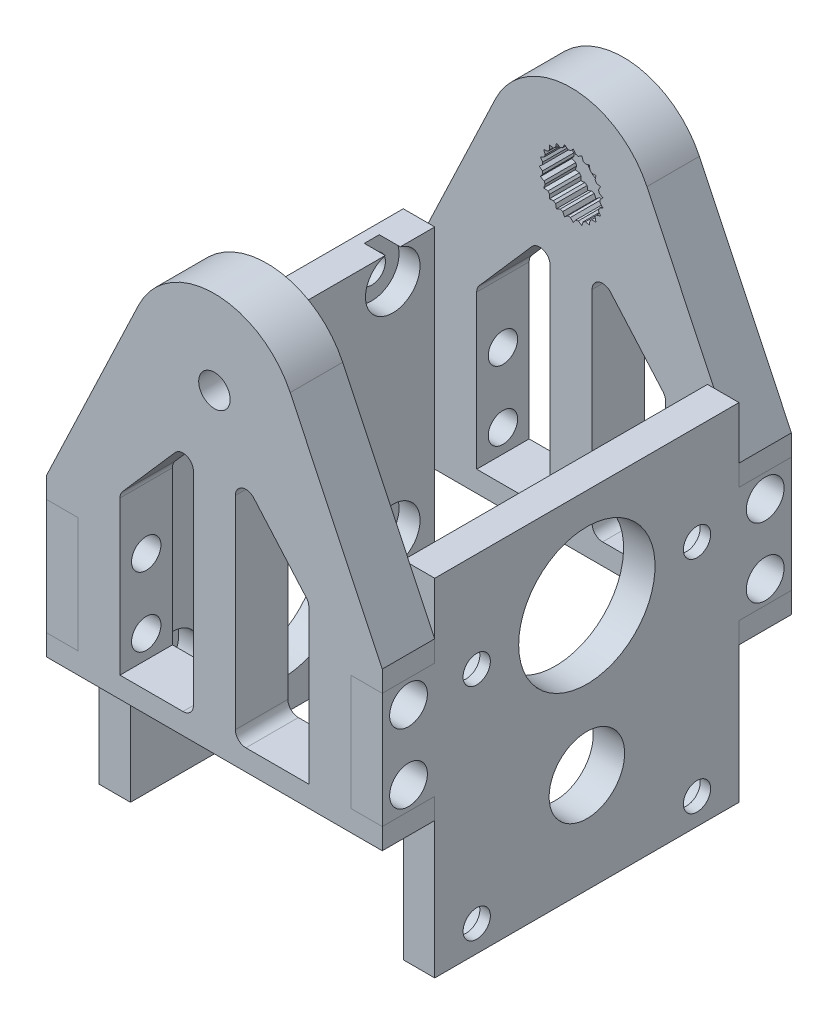
SolidWorks part; units mm, degrees
ref_plane "正面" through (0, 0, 0) normal (0, 0, 1) x (1, 0, 0)
ref_plane "平面" through (0, 0, 0) normal (0, 1, 0) x (1, 0, 0)
ref_plane "右側面" through (0, 0, 0) normal (1, 0, 0) x (0, 0, -1)
sketch "ｽｹｯﾁ1" plane through (0, 0, 0) normal (0, 0, 1) x (1, 0, 0)
  line L0 (-16, -15) -> (-16, -30)
  line L1 (-16, -30) -> (16, -30)
  line L2 (16, -30) -> (16, -15)
  line L3 (16, -15) -> (7.2234, 3.4383)
  line L4 (-7.2234, 3.4383) -> (-16, -15)
  line L5 (0, 0) -> (0, -30) construction
  line L6 (-16, -15) -> (16, -15) construction
  circle A0 centre (0, 0) radius 2.75
  arc A1 (7.2234, 3.4383) -> (-7.2234, 3.4383) centre (0, 0) ccw
  dimension "D1" = 5.5
  dimension "D6" = 8
  dimension "D2" = 16
  dimension "D3" = 16
  dimension "D4" = 15
  dimension "D5" = 15
extrude "ﾎﾞｽ - 押し出し1" add sketch "ｽｹｯﾁ1" along normal blind 3
sketch "ｽｹｯﾁ19" plane through (0, 0, 3) normal (0, 0, 1) x (1, 0, 0)
  line L0 (0, 0) -> (0, 2.75) construction
  line L1 (0, 0) -> (0.3745, 2.7244) construction
  line L2 (0, 0) -> (0.7419, 2.648) construction
  line L3 (0, 0) -> (1.0956, 2.5223) construction
  line L4 (0, 0) -> (1.4289, 2.3497) construction
  line L5 (0, 0) -> (1.7355, 2.1332) construction
  line L6 (0, 0) -> (2.0098, 1.877) construction
  line L7 (0, 0) -> (2.2467, 1.5859) construction
  line L8 (0, 0) -> (2.4417, 1.2652) construction
  line L9 (0, 0) -> (2.5912, 0.9209) construction
  line L10 (0, 0) -> (2.6925, 0.5595) construction
  line L11 (0, 0) -> (2.7436, 0.1877) construction
  line L12 (0, 0) -> (2.7436, -0.1877) construction
  line L13 (0, 0) -> (2.6925, -0.5595) construction
  line L14 (0, 0) -> (2.5912, -0.9209) construction
  line L15 (0, 0) -> (2.4417, -1.2652) construction
  line L16 (0, 0) -> (2.2467, -1.5859) construction
  line L17 (0, 0) -> (2.0098, -1.877) construction
  line L18 (0, 0) -> (1.7355, -2.1332) construction
  line L19 (0, 0) -> (1.4289, -2.3497) construction
  line L20 (0, 0) -> (1.0956, -2.5223) construction
  line L21 (0, 0) -> (0.7419, -2.648) construction
  line L22 (0, 0) -> (0.3745, -2.7244) construction
  line L23 (0, 0) -> (0, -2.75) construction
  line L24 (0, 0) -> (-0.3745, -2.7244) construction
  line L25 (0, 0) -> (-0.7419, -2.648) construction
  line L26 (0, 0) -> (-1.0956, -2.5223) construction
  line L27 (0, 0) -> (-1.4289, -2.3497) construction
  line L28 (0, 0) -> (-1.7355, -2.1332) construction
  line L29 (0, 0) -> (-2.0098, -1.877) construction
  line L30 (0, 0) -> (-2.2467, -1.5859) construction
  line L31 (0, 0) -> (-2.4417, -1.2652) construction
  line L32 (0, 0) -> (-2.5912, -0.9209) construction
  line L33 (0, 0) -> (-2.6925, -0.5595) construction
  line L34 (0, 0) -> (-2.7436, -0.1877) construction
  line L35 (0, 0) -> (-2.7436, 0.1877) construction
  line L36 (0, 0) -> (-2.6925, 0.5595) construction
  line L37 (0, 0) -> (-2.5912, 0.9209) construction
  line L38 (0, 0) -> (-2.4417, 1.2652) construction
  line L39 (0, 0) -> (-2.2467, 1.5859) construction
  line L40 (0, 0) -> (-2.0098, 1.877) construction
  line L41 (0, 0) -> (-1.7355, 2.1332) construction
  line L42 (0, 0) -> (-1.4289, 2.3497) construction
  line L43 (0, 0) -> (-1.0956, 2.5223) construction
  line L44 (0, 0) -> (-0.7419, 2.648) construction
  line L45 (0, 0) -> (-0.3745, 2.7244) construction
  line L46 (0, 0) -> (0.2081, 3.0429) construction
  line L47 (0.2081, 3.0429) -> (-0.0626, 2.7493)
  line L48 (0.2081, 3.0429) -> (0.4364, 2.7152)
  line L49 (-0.0626, 2.7493) -> (0, 0) construction
  line L50 (0, 0) -> (0.4364, 2.7152) construction
  line L51 (1.0214, 2.8739) -> (0.6815, 2.6642)
  line L52 (1.0214, 2.8739) -> (1.1527, 2.4967)
  line L53 (1.7589, 2.4918) -> (1.375, 2.3816)
  line L54 (1.7589, 2.4918) -> (1.7836, 2.0931)
  line L55 (2.3659, 1.9248) -> (1.9666, 1.9223)
  line L56 (2.3659, 1.9248) -> (2.2822, 1.5343)
  line L57 (2.7975, 1.2151) -> (2.4123, 1.3204)
  line L58 (2.7975, 1.2151) -> (2.6115, 0.8617)
  line L59 (3.0216, 0.4153) -> (2.679, 0.6206)
  line L60 (3.0216, 0.4153) -> (2.7472, 0.1252)
  line L61 (3.0216, -0.4153) -> (2.7472, -0.1252)
  line L62 (3.0216, -0.4153) -> (2.679, -0.6206)
  line L63 (2.7975, -1.2151) -> (2.6115, -0.8617)
  line L64 (2.7975, -1.2151) -> (2.4123, -1.3204)
  line L65 (2.3659, -1.9248) -> (2.2822, -1.5343)
  line L66 (2.3659, -1.9248) -> (1.9666, -1.9223)
  line L67 (1.7589, -2.4918) -> (1.7836, -2.0931)
  line L68 (1.7589, -2.4918) -> (1.375, -2.3816)
  line L69 (1.0214, -2.8739) -> (1.1527, -2.4967)
  line L70 (1.0214, -2.8739) -> (0.6815, -2.6642)
  line L71 (0.2081, -3.0429) -> (0.4364, -2.7152)
  line L72 (0.2081, -3.0429) -> (-0.0626, -2.7493)
  line L73 (-0.6205, -2.9862) -> (-0.3123, -2.7322)
  line L74 (-0.6205, -2.9862) -> (-0.802, -2.6304)
  line L75 (-1.4032, -2.708) -> (-1.0379, -2.5466)
  line L76 (-1.4032, -2.708) -> (-1.482, -2.3165)
  line L77 (-2.0818, -2.229) -> (-1.6865, -2.1722)
  line L78 (-2.0818, -2.229) -> (-2.052, -1.8308)
  line L79 (-2.606, -1.5847) -> (-2.21, -1.6366)
  line L80 (-2.606, -1.5847) -> (-2.4699, -1.2093)
  line L81 (-2.9369, -0.8229) -> (-2.5696, -0.9797)
  line L82 (-2.9369, -0.8229) -> (-2.7045, -0.4981)
  line L83 (-3.05, 0) -> (-2.7386, -0.2501)
  line L84 (-3.05, 0) -> (-2.7386, 0.2501)
  line L85 (-2.9369, 0.8229) -> (-2.7045, 0.4981)
  line L86 (-2.9369, 0.8229) -> (-2.5696, 0.9797)
  line L87 (-2.606, 1.5847) -> (-2.4699, 1.2093)
  line L88 (-2.606, 1.5847) -> (-2.21, 1.6366)
  line L89 (-2.0818, 2.229) -> (-2.052, 1.8308)
  line L90 (-2.0818, 2.229) -> (-1.6865, 2.1722)
  line L91 (-1.4032, 2.708) -> (-1.482, 2.3165)
  line L92 (-1.4032, 2.708) -> (-1.0379, 2.5466)
  line L93 (-0.6205, 2.9862) -> (-0.802, 2.6304)
  line L94 (-0.6205, 2.9862) -> (-0.3123, 2.7322)
  circle A0 centre (0, 0) radius 2.75 construction
  arc A1 (0, 2.75) -> (0.3745, 2.7244) centre (0, 0) cw construction
  circle A2 centre (0, 0) radius 3.05 construction
  arc A3 (-0.0626, 2.7493) -> (0.4364, 2.7152) centre (0, 0) cw
  arc A4 (0.6815, 2.6642) -> (1.1527, 2.4967) centre (0, 0) cw
  arc A5 (1.375, 2.3816) -> (1.7836, 2.0931) centre (0, 0) cw
  arc A6 (1.9666, 1.9223) -> (2.2822, 1.5343) centre (0, 0) cw
  arc A7 (2.4123, 1.3204) -> (2.6115, 0.8617) centre (0, 0) cw
  arc A8 (2.679, 0.6206) -> (2.7472, 0.1252) centre (0, 0) cw
  arc A9 (2.7472, -0.1252) -> (2.679, -0.6206) centre (0, 0) cw
  arc A10 (2.6115, -0.8617) -> (2.4123, -1.3204) centre (0, 0) cw
  arc A11 (2.2822, -1.5343) -> (1.9666, -1.9223) centre (0, 0) cw
  arc A12 (1.7836, -2.0931) -> (1.375, -2.3816) centre (0, 0) cw
  arc A13 (1.1527, -2.4967) -> (0.6815, -2.6642) centre (0, 0) cw
  arc A14 (0.4364, -2.7152) -> (-0.0626, -2.7493) centre (0, 0) cw
  arc A15 (-0.3123, -2.7322) -> (-0.802, -2.6304) centre (0, 0) cw
  arc A16 (-1.0379, -2.5466) -> (-1.482, -2.3165) centre (0, 0) cw
  arc A17 (-1.6865, -2.1722) -> (-2.052, -1.8308) centre (0, 0) cw
  arc A18 (-2.21, -1.6366) -> (-2.4699, -1.2093) centre (0, 0) cw
  arc A19 (-2.5696, -0.9797) -> (-2.7045, -0.4981) centre (0, 0) cw
  arc A20 (-2.7386, -0.2501) -> (-2.7386, 0.2501) centre (0, 0) cw
  arc A21 (-2.7045, 0.4981) -> (-2.5696, 0.9797) centre (0, 0) cw
  arc A22 (-2.4699, 1.2093) -> (-2.21, 1.6366) centre (0, 0) cw
  arc A23 (-2.052, 1.8308) -> (-1.6865, 2.1722) centre (0, 0) cw
  arc A24 (-1.482, 2.3165) -> (-1.0379, 2.5466) centre (0, 0) cw
  arc A25 (-0.802, 2.6304) -> (-0.3123, 2.7322) centre (0, 0) cw
  point P7 (0.1877, 2.7436)
  point P52 (0, 0)
  point P60 (0.1877, 2.7436)
  point P126 (0, 0)
  dimension "D2" = 6.1
  dimension "D3" = 10.435
  dimension "D1" = 46
  dimension "D4" = 23
extrude "ｶｯﾄ - 押し出し6" cut sketch "ｽｹｯﾁ19" against normal through all
sketch "ｽｹｯﾁ2" plane through (0, 0, 0) normal (0, 0, -1) x (-1, 0, 0)
  line L5 (16, -15) -> (7.2234, 3.4383)
  line L6 (-7.2234, 3.4383) -> (-16, -15)
  line L7 (-16, -15) -> (-16, -30)
  line L8 (-16, -30) -> (16, -30)
  line L9 (16, -30) -> (16, -15)
  line L10 (16, -15) -> (7.2234, 3.4383)
  line L11 (-7.2234, 3.4383) -> (-16, -15)
  line L12 (-16, -15) -> (-16, -30)
  line L13 (-16, -30) -> (16, -30)
  line L14 (16, -30) -> (16, -15)
  arc A1 (7.2234, 3.4383) -> (-7.2234, 3.4383) centre (0, 0) ccw
  arc A2 (7.2234, 3.4383) -> (-7.2234, 3.4383) centre (0, 0) ccw
  dimension "D1" = 0
extrude "ﾎﾞｽ - 押し出し2" add sketch "ｽｹｯﾁ2" along normal blind 2
ref_plane "平面1" through (0, 0, 33.5) normal (0, 0, 1) x (1, 0, 0)
sketch "ｽｹｯﾁ3" plane through (0, 0, 33.5) normal (0, 0, 1) x (1, 0, 0)
  line L5 (-7.2234, 3.4383) -> (-16, -15)
  line L6 (-16, -15) -> (-16, -30)
  line L7 (-16, -30) -> (16, -30)
  line L8 (16, -30) -> (16, -15)
  line L9 (16, -15) -> (7.2234, 3.4383)
  line L10 (-7.2234, 3.4383) -> (-16, -15)
  line L11 (-16, -15) -> (-16, -30)
  line L12 (-16, -30) -> (16, -30)
  line L13 (16, -30) -> (16, -15)
  line L14 (16, -15) -> (7.2234, 3.4383)
  circle A0 centre (0, 0) radius 2.75 construction
  arc A1 (7.2234, 3.4383) -> (-7.2234, 3.4383) centre (0, 0) ccw
  arc A2 (7.2234, 3.4383) -> (-7.2234, 3.4383) centre (0, 0) ccw
  circle A3 centre (0, 0) radius 2.75 construction
  circle A4 centre (0, 0) radius 3.6
  dimension "D2" = 7.2
  dimension "D1" = 0
extrude "ﾎﾞｽ - 押し出し3" add sketch "ｽｹｯﾁ3" against normal blind 1.5 separate body
sketch "ｽｹｯﾁ4" plane through (0, 0, 33.5) normal (0, 0, 1) x (1, 0, 0)
  line L5 (-7.2234, 3.4383) -> (-16, -15)
  line L6 (-16, -15) -> (-16, -30)
  line L7 (-16, -30) -> (16, -30)
  line L8 (16, -30) -> (16, -15)
  line L9 (16, -15) -> (7.2234, 3.4383)
  line L10 (-7.2234, 3.4383) -> (-16, -15)
  line L11 (-16, -15) -> (-16, -30)
  line L12 (-16, -30) -> (16, -30)
  line L13 (16, -30) -> (16, -15)
  line L14 (16, -15) -> (7.2234, 3.4383)
  arc A1 (7.2234, 3.4383) -> (-7.2234, 3.4383) centre (0, 0) ccw
  arc A2 (7.2234, 3.4383) -> (-7.2234, 3.4383) centre (0, 0) ccw
  dimension "D1" = 0
extrude "ﾎﾞｽ - 押し出し4" add sketch "ｽｹｯﾁ4" along normal blind 3.5
sketch "ｽｹｯﾁ5" plane through (0, 0, -2) normal (0, 0, -1) x (-1, 0, 0)
  line L0 (-16, -15) -> (-16, -30) construction
  line L1 (-16, -17) -> (-13, -17)
  line L2 (-16, -17) -> (-16, -28)
  line L3 (-16, -28) -> (-13, -28)
  line L4 (-13, -17) -> (-13, -28)
  line L5 (-16, -17) -> (-13, -28) construction
  line L6 (-16, -28) -> (-13, -17) construction
  line L7 (16, -30) -> (16, -15) construction
  line L8 (16, -17) -> (13, -17)
  line L9 (16, -17) -> (16, -28)
  line L10 (16, -28) -> (13, -28)
  line L11 (13, -17) -> (13, -28)
  line L12 (16, -17) -> (13, -28) construction
  line L13 (16, -28) -> (13, -17) construction
  line L14 (-16, -30) -> (16, -30) construction
  line L15 (-16, -15) -> (16, -15) construction
  line L16 (-7.2234, 3.4383) -> (-16, -15) construction
  point P4 (-14.5, -22.5)
  point P11 (14.5, -22.5)
  dimension "D1" = 3
  dimension "D2" = 3
  dimension "D3" = 2
  dimension "D4" = 2
extrude "ｶｯﾄ - 押し出し1" cut sketch "ｽｹｯﾁ5" against normal through all
sketch "ｽｹｯﾁ6" plane through (13, 0, 0) normal (1, 0, 0) x (0, 0, -1)
  line L0 (2, -17) -> (-3, -17)
  line L1 (-3, -17) -> (-3, -10)
  line L2 (-3, -10) -> (-32, -10)
  line L3 (-32, -15) -> (-32, 3.4383) construction
  line L4 (-32, -10) -> (-32, -17)
  line L5 (-32, -17) -> (-37, -17)
  line L6 (-37, -17) -> (-37, -28)
  line L7 (-37, -28) -> (-32, -28)
  line L8 (-32, -28) -> (-32, -43)
  line L9 (-32, -43) -> (-3, -43)
  line L10 (-3, -43) -> (-3, -28)
  line L11 (-3, -28) -> (2, -28)
  line L12 (2, -28) -> (2, -17)
  line L13 (-17.5, -10) -> (-17.5, -43) construction
  line L14 (0, 0) -> (-33.5, 0) construction
  line L15 (-7, -40.5) -> (-28, -40.5) construction
  line L16 (-7, -40.5) -> (-7, -19.5) construction
  line L17 (-7, -19.5) -> (-28, -19.5) construction
  line L18 (-28, -40.5) -> (-28, -19.5) construction
  line L19 (-7, -40.5) -> (-28, -19.5) construction
  line L20 (-7, -19.5) -> (-28, -40.5) construction
  line L21 (-33.5, 3.025) -> (-33.5, -3.025) construction
  line L22 (2, -26.5) -> (-37, -26.5) construction
  circle A0 centre (-17.5, -19.5) radius 6.5
  circle A1 centre (-28, -19.5) radius 1.3
  circle A2 centre (-7, -19.5) radius 1.3
  circle A3 centre (-28, -40.5) radius 1.3
  circle A4 centre (-7, -40.5) radius 1.3
  circle A5 centre (-17.5, -33.5) radius 6.5 construction
  circle A6 centre (-17.5, -33.5) radius 3.6
  point P24 (-17.5, -30)
  point P43 (-17.5, -26.5)
  dimension "D6" = 2.6
  dimension "D8" = 13
  dimension "D10" = 7.2
  dimension "D1" = 21
  dimension "D2" = 21
  dimension "D3" = 14.5
  dimension "D4" = 13
  dimension "D5" = 21
  dimension "D7" = 20
  dimension "D9" = 30
extrude "ﾎﾞｽ - 押し出し5" add sketch "ｽｹｯﾁ6" along normal up to surface (3 mm away) separate body up to face at (16, -16, 0.5)
sketch "ｽｹｯﾁ8" plane through (-13, 0, 0) normal (-1, 0, 0) x (0, 0, 1)
  line L0 (3, -10) -> (3, -43) construction
  line L1 (32, -10) -> (32, -43) construction
  line L2 (3, -26.5) -> (32, -26.5) construction
  line L12 (-2, -17) -> (-2, -28)
  line L13 (-2, -28) -> (3, -28)
  line L14 (3, -28) -> (3, -43)
  line L15 (3, -43) -> (32, -43)
  line L16 (32, -43) -> (32, -28)
  line L17 (32, -28) -> (37, -28)
  line L18 (37, -28) -> (37, -17)
  line L19 (37, -17) -> (32, -17)
  line L20 (32, -17) -> (32, -10)
  line L21 (32, -10) -> (3, -10)
  line L22 (3, -10) -> (3, -17)
  line L23 (3, -17) -> (-2, -17)
  line L24 (-2, -17) -> (-2, -28)
  line L25 (-2, -28) -> (3, -28)
  line L26 (3, -28) -> (3, -43)
  line L27 (3, -43) -> (32, -43)
  line L28 (32, -43) -> (32, -28)
  line L29 (32, -28) -> (37, -28)
  line L30 (37, -28) -> (37, -17)
  line L31 (37, -17) -> (32, -17)
  line L32 (32, -17) -> (32, -10)
  line L33 (32, -10) -> (3, -10)
  line L34 (3, -10) -> (3, -17)
  line L35 (3, -17) -> (-2, -17)
  circle A0 centre (28, -40.5) radius 1.3 construction
  circle A1 centre (28, -19.5) radius 1.3 construction
  circle A2 centre (7, -40.5) radius 1.3 construction
  circle A3 centre (17.5, -19.5) radius 6.5 construction
  circle A4 centre (7, -19.5) radius 1.3 construction
  circle A5 centre (28, -40.5) radius 1.3 construction
  circle A6 centre (28, -19.5) radius 1.3 construction
  circle A7 centre (7, -40.5) radius 1.3 construction
  circle A8 centre (17.5, -19.5) radius 6.5 construction
  circle A9 centre (7, -19.5) radius 1.3 construction
  circle A10 centre (28, -12.5) radius 1.3
  circle A11 centre (7, -12.5) radius 1.3
  circle A12 centre (28, -33.5) radius 1.3
  circle A13 centre (17.5, -33.5) radius 6.5
  circle A14 centre (7, -33.5) radius 1.3
  circle A15 centre (17.5, -19.5) radius 3.6
  dimension "D2" = 7.2
  dimension "D1" = 0
extrude "ﾎﾞｽ - 押し出し6" add sketch "ｽｹｯﾁ8" along normal up to surface (3 mm away) separate body up to face at (-16, -29, 0.5)
sketch "ｽｹｯﾁ7" plane through (0, 0, -2) normal (0, 0, -1) x (-1, 0, 0)
  line L0 (0, 0) -> (0, -16.5) construction
  line L1 (-16, -30) -> (16, -30) construction
  line L2 (9, -28) -> (-9, -28) construction
  line L3 (9, -28) -> (9, -5) construction
  line L4 (9, -5) -> (-9, -5) construction
  line L5 (-9, -28) -> (-9, -5) construction
  line L6 (9, -28) -> (-9, -5) construction
  line L7 (9, -5) -> (-9, -28) construction
  line L8 (-13, -28) -> (-13, -17) construction
  line L9 (-9, -28) -> (-3, -28)
  line L10 (-2, -27) -> (-2, -7.6614)
  line L11 (-3.7526, -7.0029) -> (-8.7526, -12.7172)
  line L12 (-9, -13.3757) -> (-9, -28)
  line L15 (-16, -17) -> (-13, -17) construction
  line L16 (9, -28) -> (3, -28)
  line L17 (9, -13.3757) -> (9, -28)
  line L18 (3.7526, -7.0029) -> (8.7526, -12.7172)
  line L19 (2, -27) -> (2, -7.6614)
  circle A0 centre (0, 0) radius 1.5
  arc A2 (3, -28) -> (2, -27) centre (3, -27) cw
  arc A3 (-3, -28) -> (-2, -27) centre (-3, -27) ccw
  arc A5 (-2, -7.6614) -> (-3.7526, -7.0029) centre (-3, -7.6614) ccw
  arc A6 (3.7526, -7.0029) -> (2, -7.6614) centre (3, -7.6614) ccw
  arc A7 (9, -13.3757) -> (8.7526, -12.7172) centre (8, -13.3757) ccw
  arc A8 (-8.7526, -12.7172) -> (-9, -13.3757) centre (-8, -13.3757) ccw
  point P28 (2, -28)
  point P31 (-2, -28)
  point P37 (-2, -5)
  point P40 (2, -5)
  point P43 (9, -13)
  point P46 (-9, -13)
  dimension "D1" = 3
  dimension "D8" = 1
  dimension "D2" = 2
  dimension "D3" = 4
  dimension "D4" = 23
  dimension "D5" = 4
  dimension "D6" = 7
extrude "ｶｯﾄ - 押し出し2" cut sketch "ｽｹｯﾁ7" against normal through all
sketch "ｽｹｯﾁ10" plane through (16, 0, 0) normal (1, 0, 0) x (0, 0, -1)
  line L4 (-34.5, -15) -> (-34.5, -30) construction
  line L5 (-32, -15) -> (-37, -15) construction
  line L6 (-32, -30) -> (-37, -30) construction
  line L8 (-0.5, -15) -> (-0.5, -30) construction
  line L9 (-3, -15) -> (2, -15) construction
  line L10 (-3, -30) -> (2, -30) construction
  line L11 (-37, -17) -> (-32, -17) construction
  line L14 (-32, -28) -> (-37, -28) construction
  line L15 (-3, -17) -> (2, -17) construction
  line L16 (2, -28) -> (-3, -28) construction
  point P26 (-34.5, -19.2)
  point P28 (-34.5, -25.8)
  point P30 (-0.5, -19.2)
  point P32 (-0.5, -25.8)
  dimension "D1" = 2.2
  dimension "D2" = 2.2
  dimension "D3" = 2.2
  dimension "D4" = 2.2
hole_wizard "Ø2.8 (2.8) 直径の穴1" positions "ｽｹｯﾁ10" profile "ｽｹｯﾁ11" hole size "Ø2.8" standard "JIS"
sketch "ｽｹｯﾁ11" plane through (16, -25.8, 0.5) normal (0, 1, 0) x (0, 0, -1)
  line L0 (0, 0) -> (0, 14)
  line L1 (0, 14) -> (1.4, 13.1588)
  line L2 (1.4, 13.1588) -> (1.4, 0)
  line L5 (1.4, 0) -> (0, 0)
  line L10 (0, 14) -> (-1.4, 13.1588) construction
  line L11 (0, -6.35) -> (0, 107.95) construction
  dimension "穴の直径" = 2.8
  dimension "穴の深さ" = 14
  dimension "ﾄﾞﾘﾙ角度" = 118
hole_wizard "Ø2.8 (2.8) 直径の穴2" positions "ｽｹｯﾁ12" profile "ｽｹｯﾁ13" hole size "Ø2.8" standard "JIS"
sketch "ｽｹｯﾁ12" plane through (-16, 0, 0) normal (-1, 0, 0) x (0, 0, 1)
  point P0 (34.5, -19.2)
  point P3 (34.5, -25.8)
  point P6 (0.5, -19.2)
  point P9 (0.5, -25.8)
sketch "ｽｹｯﾁ13" plane through (-16, -19.2, 34.5) normal (0, 1, 0) x (0, 0, 1)
  line L0 (0, 0) -> (0, 14)
  line L1 (0, 14) -> (1.4, 13.1588)
  line L2 (1.4, 13.1588) -> (1.4, 0)
  line L5 (1.4, 0) -> (0, 0)
  line L10 (0, 14) -> (-1.4, 13.1588) construction
  line L11 (0, -6.35) -> (0, 107.95) construction
  dimension "穴の直径" = 2.8
  dimension "穴の深さ" = 14
  dimension "ﾄﾞﾘﾙ角度" = 118
hole_wizard "Ø3.6 (3.6) 直径の穴1" positions "ｽｹｯﾁ14" profile "ｽｹｯﾁ16" hole size "Ø3.6" standard "JIS" end condition through all
sketch "ｽｹｯﾁ14" plane through (16, 0, 0) normal (1, 0, 0) x (0, 0, -1)
  point P0 (-34.5, -19.2)
  point P3 (-34.5, -25.8)
  point P6 (-0.5, -19.2)
  point P9 (-0.5, -25.8)
sketch "ｽｹｯﾁ16" plane through (16, -19.2, 34.5) normal (0, 1, 0) x (0, 0, -1)
  line L0 (0, 0) -> (0, 32)
  line L1 (0, 32) -> (1.8, 32)
  line L2 (1.8, 32) -> (1.8, 0)
  line L5 (1.8, 0) -> (0, 0)
  line L11 (0, -6.35) -> (0, 107.95) construction
  dimension "通し穴の直径" = 3.6
  dimension "通し穴の深さ" = 32
sketch "ｽｹｯﾁ17" plane through (13, 0, 0) normal (-1, 0, 0) x (0, 0, 1)
  circle A0 centre (28, -40.5) radius 1.3 construction
  circle A1 centre (7, -40.5) radius 1.3 construction
  circle A2 centre (28, -19.5) radius 1.3 construction
  circle A3 centre (7, -19.5) radius 1.3 construction
  circle A4 centre (28, -40.5) radius 1.3 construction
  circle A5 centre (7, -40.5) radius 1.3 construction
  circle A6 centre (28, -19.5) radius 1.3 construction
  circle A7 centre (7, -19.5) radius 1.3 construction
  circle A8 centre (7, -19.5) radius 2.6
  circle A9 centre (7, -40.5) radius 2.6
  circle A10 centre (28, -40.5) radius 2.6
  circle A11 centre (28, -19.5) radius 2.6
  dimension "D1" = 5.2
extrude "ｶｯﾄ - 押し出し4" cut sketch "ｽｹｯﾁ17" against normal blind 2
sketch "ｽｹｯﾁ18" plane through (-13, 0, 0) normal (1, 0, 0) x (0, 0, -1)
  circle A0 centre (-28, -33.5) radius 1.3 construction
  circle A1 centre (-28, -12.5) radius 1.3 construction
  circle A2 centre (-7, -12.5) radius 1.3 construction
  circle A3 centre (-28, -33.5) radius 1.3 construction
  circle A4 centre (-28, -12.5) radius 1.3 construction
  circle A5 centre (-7, -12.5) radius 1.3 construction
  circle A6 centre (-7, -33.5) radius 1.3 construction
  circle A7 centre (-7, -33.5) radius 1.3 construction
  circle A8 centre (-28, -12.5) radius 2.6
  circle A9 centre (-28, -33.5) radius 2.6
  circle A10 centre (-7, -33.5) radius 2.6
  circle A11 centre (-7, -12.5) radius 2.6
  dimension "D1" = 5.2
extrude "ｶｯﾄ - 押し出し5" cut sketch "ｽｹｯﾁ18" against normal blind 2
equation "\"D2@ｽｹｯﾁ5\"=\"D1@ｽｹｯﾁ5\""
equation "\"D8@ｽｹｯﾁ6\"=12.5+0.5"
equation "\"D1@ｽｹｯﾁ10\"=\"D2@ｽｹｯﾁ10\""
equation "\"D3@ｽｹｯﾁ10\"=\"D2@ｽｹｯﾁ10\""
equation "\"D4@ｽｹｯﾁ10\"=\"D2@ｽｹｯﾁ10\""
equation "\"D3@ｽｹｯﾁ19\"=360/23*2/3"
